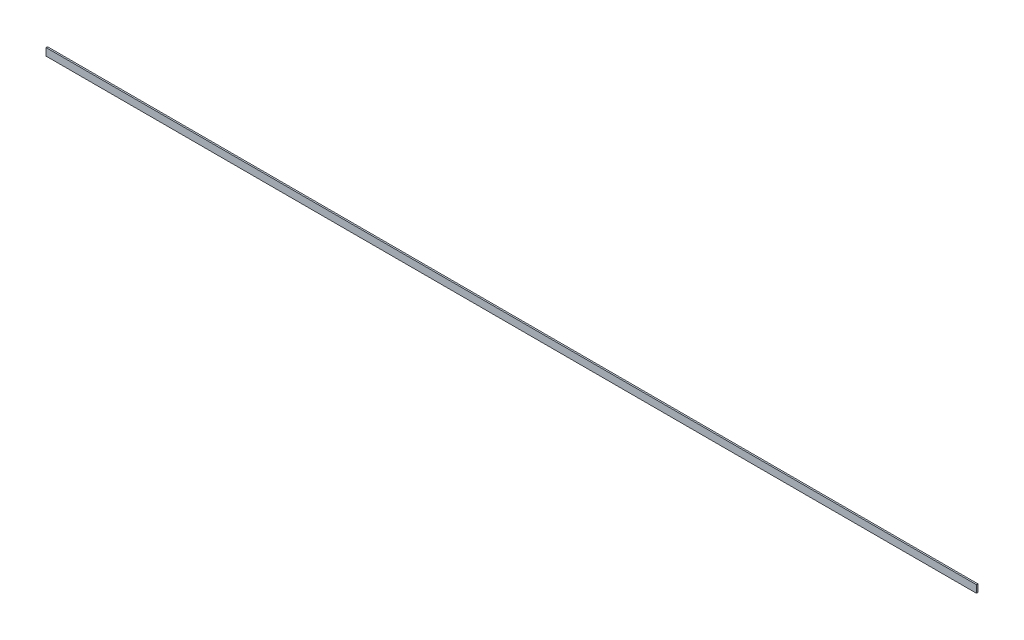
SolidWorks part; units mm, degrees
ref_plane "Спереди" through (0, 0, 0) normal (0, 0, 1) x (1, 0, 0)
ref_plane "Сверху" through (0, 0, 0) normal (0, 1, 0) x (1, 0, 0)
ref_plane "Справа" through (0, 0, 0) normal (1, 0, 0) x (0, 0, -1)
sketch "Эскиз1" plane through (0, 0, 0) normal (1, 0, 0) x (0, 0, -1)
  line L1 (0, 0) -> (4, 0)
  line L2 (0, 0) -> (0, 20)
  line L3 (0, 20) -> (4, 20)
  line L4 (4, 0) -> (4, 20)
extrude "Бобышка-Вытянуть1" add sketch "Эскиз1" along normal blind 2500
